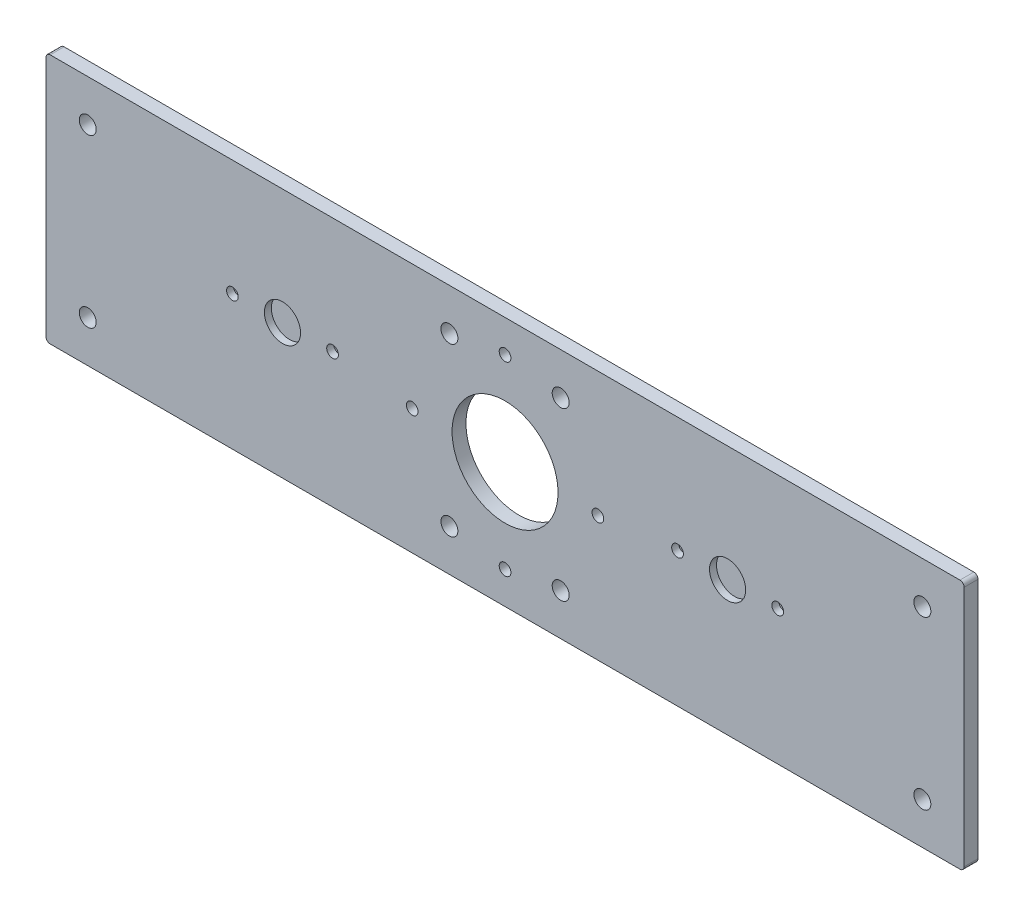
SolidWorks part; units mm, degrees
ref_plane "Front Plane" through (0, 0, 0) normal (0, 0, 1) x (1, 0, 0)
ref_plane "Top Plane" through (0, 0, 0) normal (0, 1, 0) x (1, 0, 0)
ref_plane "Right Plane" through (0, 0, 0) normal (1, 0, 0) x (0, 0, -1)
sketch "Sketch1" plane through (0, 0, 0) normal (0, 0, 1) x (1, 0, 0)
  line L0 (-165, 0) -> (165, 0) construction
  line L1 (165, -45) -> (-165, -45)
  line L2 (165, -45) -> (165, 45)
  line L3 (165, 45) -> (-165, 45)
  line L4 (-165, -45) -> (-165, 45)
  line L5 (165, -45) -> (-165, 45) construction
  line L6 (165, 45) -> (-165, -45) construction
  line L8 (0, -33.3754) -> (33.3754, 0) construction
  line L9 (0, -33.3754) -> (-33.3754, 0) construction
  line L10 (-33.3754, 0) -> (0, 33.3754) construction
  line L11 (33.3754, 0) -> (0, 33.3754) construction
  line L12 (0, -33.3754) -> (0, 33.3754) construction
  line L13 (-33.3754, 0) -> (33.3754, 0) construction
  circle A0 centre (0, 0) radius 19.05
  circle A1 centre (-33.3754, 0) radius 2.1
  circle A2 centre (33.3754, 0) radius 2.1
  circle A3 centre (0, 33.3754) radius 2.1
  circle A4 centre (0, -33.3754) radius 2.1
  point P0 (0, 0)
  dimension "D3" = 38.1
  dimension "D4" = 47.2
  dimension "D5" = 47.2
  dimension "D8" = 4.2
  dimension "D9" = 4.2
  dimension "D10" = 4.2
  dimension "D11" = 4.2
  dimension "D1" = 90
  dimension "D2" = 330
  dimension "D6" = 90
  dimension "D7" = 90
extrude "Boss-Extrude1" add sketch "Sketch1" along normal mid plane 5
sketch "Sketch2" plane through (0, 0, 2.5) normal (0, 0, 1) x (1, 0, 0)
  line L2 (-150, 45) -> (-150, -45)
  line L3 (-150, 45) -> (-150, -45) construction
  line L5 (150, -45) -> (150, 45)
  line L6 (150, -45) -> (150, 45) construction
  line L23 (165, 30) -> (-165, 30)
  line L24 (165, 30) -> (-165, 30) construction
  line L25 (0, 45) -> (0, -45) construction
  line L26 (-165, -30) -> (165, -30)
  line L27 (-165, -30) -> (165, -30) construction
  line L28 (165, 45) -> (-165, 45) construction
  line L29 (-165, -45) -> (165, -45) construction
  line L30 (-20, 45) -> (-20, -45) construction
  line L31 (20, 45) -> (20, -45) construction
  circle A0 centre (-150, 30) radius 3.05
  circle A1 centre (-150, -30) radius 3.05
  circle A2 centre (-20, 30) radius 3.05
  circle A3 centre (-20, -30) radius 3.05
  circle A4 centre (20, -30) radius 3.05
  circle A5 centre (20, 30) radius 3.05
  circle A6 centre (150, 30) radius 3.05
  circle A7 centre (150, -30) radius 3.05
  dimension "D7" = 6.1
  dimension "D8" = 6.1
  dimension "D9" = 6.1
  dimension "D10" = 6.1
  dimension "D11" = 6.1
  dimension "D12" = 6.1
  dimension "D13" = 6.1
  dimension "D14" = 6.1
  dimension "D1" = 15
  dimension "D2" = 15
  dimension "D3" = 15
  dimension "D4" = 15
  dimension "D5" = 20
  dimension "D6" = 20
extrude "Cut-Extrude1" cut sketch "Sketch2" against normal through all
sketch "Sketch3" plane through (0, 0, 2.5) normal (0, 0, 1) x (1, 0, 0)
  line L0 (0, 3.4) -> (-49.4534, 3.4) construction
  circle A0 centre (-62, 3.4) radius 2.1
  circle A1 centre (-98, 3.4) radius 2.1
  circle A2 centre (-80, 3.4) radius 6.5
  dimension "D1" = 4.2
  dimension "D2" = 4.2
  dimension "D3" = 13
  dimension "D4" = 80
  dimension "D5" = 18
  dimension "D6" = 18
  dimension "D7" = 3.4
extrude "Cut-Extrude2" cut sketch "Sketch3" against normal up to vertex (2.5 mm away) up to point (0, 0, 0)
mirror "Mirror1" about plane through (0, 0, 0) normal (1, 0, 0) of "Cut-Extrude2"
fillet "Fillet1" radius 1.5 4 edges at (-165, -45, 0) (165, -45, 0) (165, 45, 0) (-165, 45, 0)
equation "\"D4@Sketch3\"=160/2"
equation "\"D9@Sketch2\"=\"D7@Sketch2\""
equation "\"D12@Sketch2\"=\"D7@Sketch2\""
equation "\"D13@Sketch2\"=\"D7@Sketch2\""
equation "\"D8@Sketch2\"=\"D7@Sketch2\""
equation "\"D10@Sketch2\"=\"D7@Sketch2\""
equation "\"D11@Sketch2\"=\"D7@Sketch2\""
equation "\"D14@Sketch2\"=\"D7@Sketch2\""
equation "\"D9@Sketch1\"=\"D8@Sketch1\""
equation "\"D10@Sketch1\"=\"D8@Sketch1\""
equation "\"D11@Sketch1\"=\"D8@Sketch1\""
